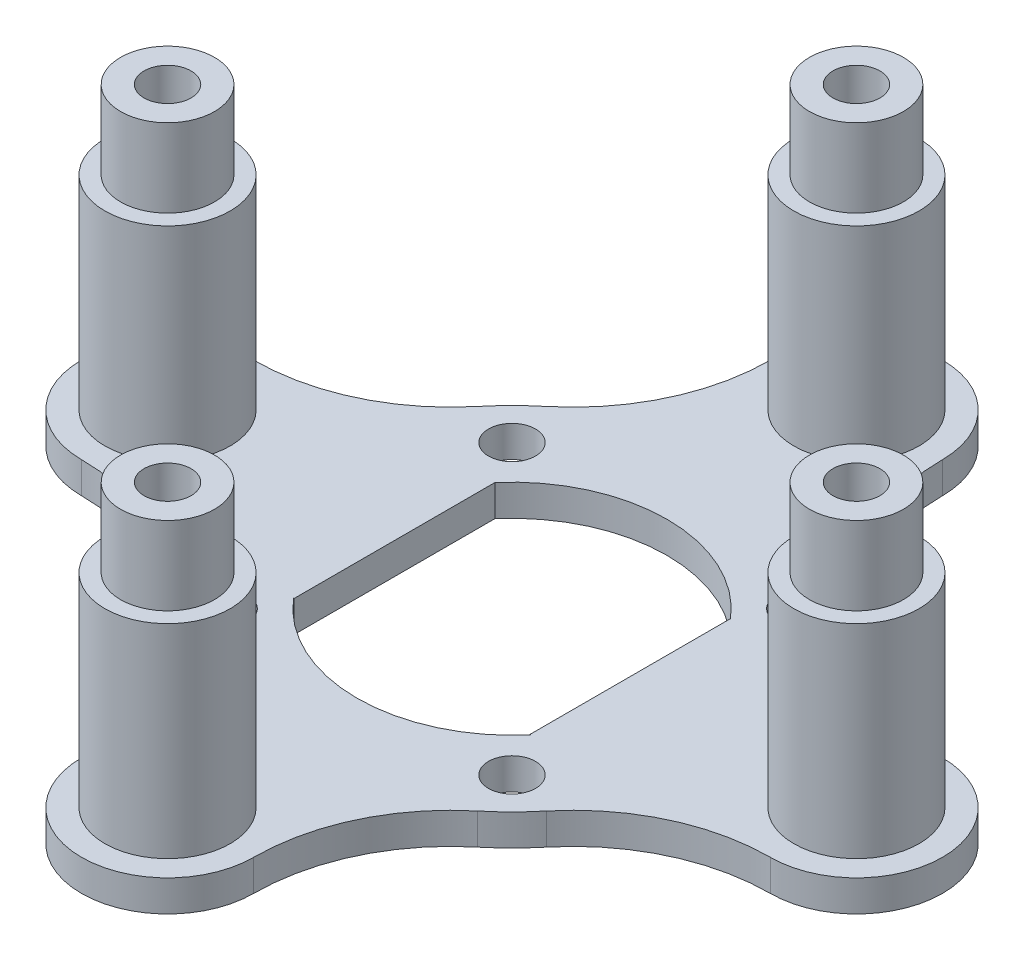
SolidWorks part; units mm, degrees
ref_plane "Front Plane" through (0, 0, 0) normal (0, 0, 1) x (1, 0, 0)
ref_plane "Top Plane" through (0, 0, 0) normal (0, 1, 0) x (1, 0, 0)
ref_plane "Right Plane" through (0, 0, 0) normal (1, 0, 0) x (0, 0, -1)
sketch "Sketch1" plane through (0, 0, 0) normal (0, 1, 0) x (1, 0, 0)
  line L0 (-7.5263, -6.3887) -> (-7.5627, -6.3887)
  line L1 (7.5627, -6.3887) -> (7.5263, -6.3887)
  line L2 (7.5263, -6.3887) -> (7.5263, 6.4316)
  line L3 (-7.5263, 6.4316) -> (-7.5263, -6.3887)
  line L4 (-9.1924, 9.1924) -> (-9.1924, -9.1924) construction
  line L5 (-9.1924, 9.1924) -> (9.1924, 9.1924) construction
  line L6 (-9.1924, -9.1924) -> (9.1924, -9.1924) construction
  line L7 (9.1924, 9.1924) -> (9.1924, -9.1924) construction
  line L8 (-9.1924, 9.1924) -> (9.1924, -9.1924) construction
  line L9 (-9.1924, -9.1924) -> (9.1924, 9.1924) construction
  arc A0 (-7.5627, -6.3887) -> (7.5627, -6.3887) centre (0, 0) ccw
  arc A1 (7.5263, 6.4316) -> (-7.5263, 6.4316) centre (0, 0) ccw
  circle A2 centre (0, 0) radius 15.9
  circle A3 centre (-9.1924, 9.1924) radius 1.5
  circle A4 centre (9.1924, 9.1924) radius 1.5
  circle A5 centre (9.1924, -9.1924) radius 1.5
  circle A6 centre (-9.1924, -9.1924) radius 1.5
  point P24 (0, 0)
  dimension "D1" = 31.8
  dimension "D3" = 9.9
  dimension "D6" = 3
  dimension "D2" = 12.8202
  dimension "D4" = 15.089
  dimension "D5" = 13
  dimension "D7" = 4
sketch "Sketch2" plane through (0, 0, 0) normal (0, 1, 0) x (1, 0, 0)
  line L0 (0, 0) -> (155.6578, 0) construction
  line L1 (-7.5263, 6.4316) -> (-7.5263, -6.3887) construction
  line L2 (-7.5263, -6.3887) -> (-7.5627, -6.3887) construction
  line L3 (7.5627, -6.3887) -> (7.5263, -6.3887) construction
  line L4 (7.5263, -6.3887) -> (7.5263, 6.4316) construction
  line L5 (-7.5263, 6.4316) -> (-7.5263, -6.3887)
  line L6 (-7.5263, -6.3887) -> (-7.5627, -6.3887)
  line L7 (7.5627, -6.3887) -> (7.5263, -6.3887)
  line L8 (7.5263, -6.3887) -> (7.5263, 6.4316)
  circle A0 centre (22, 0) radius 1.5
  circle A1 centre (22, 0) radius 4
  circle A2 centre (22, 0) radius 3
  circle A12 centre (22, 0) radius 5.5
  arc A13 (12.2869, 10.0916) -> (22, 5.5) centre (22, 18.0692) ccw
  arc A14 (12.2869, -10.0916) -> (22, -5.5) centre (22, -18.0692) cw
  circle A15 centre (0, 0) radius 15.9 construction
  circle A16 centre (0, 0) radius 15.9
  arc A17 (10.0916, -12.2869) -> (5.5, -22) centre (18.0692, -22) ccw
  circle A18 centre (0, -22) radius 5.5
  circle A19 centre (0, -22) radius 4
  circle A20 centre (0, -22) radius 3
  circle A21 centre (0, -22) radius 1.5
  arc A22 (-10.0916, -12.2869) -> (-5.5, -22) centre (-18.0692, -22) cw
  arc A23 (-12.2869, -10.0916) -> (-22, -5.5) centre (-22, -18.0692) ccw
  circle A24 centre (-22, 0) radius 5.5
  circle A25 centre (-22, 0) radius 4
  circle A26 centre (-22, 0) radius 3
  circle A27 centre (-22, 0) radius 1.5
  arc A28 (-12.2869, 10.0916) -> (-22, 5.5) centre (-22, 18.0692) cw
  arc A29 (-10.0916, 12.2869) -> (-5.5, 22) centre (-18.0692, 22) ccw
  circle A30 centre (0, 22) radius 5.5
  circle A31 centre (0, 22) radius 4
  circle A32 centre (0, 22) radius 3
  circle A33 centre (0, 22) radius 1.5
  arc A34 (10.0916, 12.2869) -> (5.5, 22) centre (18.0692, 22) cw
  arc A35 (-7.5627, -6.3887) -> (7.5627, -6.3887) centre (0, 0) ccw construction
  arc A36 (7.5263, 6.4316) -> (-7.5263, 6.4316) centre (0, 0) ccw construction
  circle A37 centre (9.1924, 9.1924) radius 1.5 construction
  circle A38 centre (9.1924, -9.1924) radius 1.5 construction
  circle A39 centre (-9.1924, -9.1924) radius 1.5 construction
  circle A40 centre (-9.1924, 9.1924) radius 1.5 construction
  arc A41 (-7.5627, -6.3887) -> (7.5627, -6.3887) centre (0, 0) ccw
  arc A42 (7.5263, 6.4316) -> (-7.5263, 6.4316) centre (0, 0) ccw
  circle A43 centre (9.1924, 9.1924) radius 1.5
  circle A44 centre (9.1924, -9.1924) radius 1.5
  circle A45 centre (-9.1924, -9.1924) radius 1.5
  circle A46 centre (-9.1924, 9.1924) radius 1.5
  point P7 (0, 0)
  point P8 (0, -26.6212)
  point P12 (0, 0)
  point P19 (0, 0)
  point P54 (0, 0)
  dimension "D1" = 3
  dimension "D2" = 6
  dimension "D3" = 8
  dimension "D4" = 11
  dimension "D5" = 22
  dimension "D6" = 4
extrude "Boss-Extrude1" add sketch "Sketch2" along normal blind 2 contours A42 L8 A16 L7 A41 L6 L5 A46 A45 A44 A43 | A16 A22 A18 A17 | L0 A16 A14 A12 | A16 L0 A12 A13 | A12 L0 A1 | A1 L0 A2 | A2 L0 A0 | L0 A12 A1 | L0 A1 A2 | L0 A2 A0 | A18 A19 | A21 | A16 A34 A30 A29 | A30 A31 | A31 A32 | A32 A33 | A24 A25 | A25 A26 | A26 A27 | A16 A28 A24 A23 | A19 region at (22, 0, -1.5671) region at (24.25, 0, 0.0671) region at (22, 0, -3.0894) region at (25.5, 0, 0.0894) region at (22, 0, -4.123) region at (26.75, 0, 0.123) region at (16.6203, 0, -4.8104) region at (16.6203, 0, 4.8104) region at (14.5461, 0, -5.2079) region at (0, 0, -16.124) region at (6.5032, 0, 16.5324) region at (0, 0, -16.6556) region at (0, 0, 27.3444) region at (-16.124, 0, 0) region at (-18.2209, 0, -3.7791) region at (0, 0, 22) region at (-25.8869, 0, 0) region at (-24.9151, 0, 0) region at (-3.8869, 0, -22) region at (-2.9151, 0, -22)
extrude "Boss-Extrude2" add sketch "Sketch2<4>" along normal blind 20 contours A19 A20 | A20 A21 | L0 A1 A2 | L0 A2 A0 | A2 L0 A0 | A1 L0 A2 | A31 A32 | A32 A33 | A25 A26 | A27 | A26 region at (22, 0, -1.5671) region at (24.25, 0, 0.0671) region at (22, 0, -3.0894) region at (25.5, 0, 0.0894) region at (-3.8869, 0, 22) region at (-2.9151, 0, 22) region at (-25.8869, 0, 0) region at (-22, 0, 0) region at (-3.8869, 0, -22) region at (-2.9151, 0, -22)
sketch "Sketch2<4>" plane through (0, 0, 0) normal (0, 1, 0) x (1, 0, 0) same geometry as "Sketch2"
extrude "Cut-Extrude1" cut sketch "Sketch2<5>" against normal blind 5 from surface contours A25 A26 | A31 A32 | A1 L0 A2 | L0 A1 A2 | A19 A20 region at (22, 0, -3.0894) region at (25.5, 0, 0.0894) region at (-3.8869, 0, 22) region at (-25.8869, 0, 0) region at (-3.8869, 0, -22) starting at face at (0, 20, 26)
sketch "Sketch2<5>" plane through (0, 0, 0) normal (0, 1, 0) x (1, 0, 0) same geometry as "Sketch2"
sketch "Sketch3" plane through (0, 0, 0) normal (0, 1, 0) x (1, 0, 0)
  circle A0 centre (0, -22) radius 1.5 construction
  circle A1 centre (0, -22) radius 3 construction
  circle A2 centre (0, -22) radius 4 construction
  circle A3 centre (22, 0) radius 1.5 construction
  circle A4 centre (22, 0) radius 3 construction
  circle A5 centre (22, 0) radius 4 construction
  circle A6 centre (0, 22) radius 1.5 construction
  circle A7 centre (0, 22) radius 3 construction
  circle A8 centre (0, 22) radius 4 construction
  circle A9 centre (-22, 0) radius 1.5 construction
  circle A10 centre (-22, 0) radius 3 construction
  circle A11 centre (-22, 0) radius 4 construction
  circle A12 centre (0, -22) radius 1.5
  circle A13 centre (0, -22) radius 3
  circle A14 centre (0, -22) radius 4
  circle A15 centre (22, 0) radius 1.5
  arc A16 (22, -5.5) -> (22, 5.5) centre (22, 0) ccw
  arc A17 (12.2869, 10.0916) -> (22, 5.5) centre (22, 18.0692) ccw
  arc A18 (12.2869, 10.0916) -> (10.0916, 12.2869) centre (0, 0) ccw
  arc A19 (5.5, 22) -> (10.0916, 12.2869) centre (18.0692, 22) ccw
  arc A20 (5.5, 22) -> (-5.5, 22) centre (0, 22) ccw
  arc A21 (-10.0916, 12.2869) -> (-5.5, 22) centre (-18.0692, 22) ccw
  arc A22 (-10.0916, 12.2869) -> (-12.2869, 10.0916) centre (0, 0) ccw
  arc A23 (-22, 5.5) -> (-12.2869, 10.0916) centre (-22, 18.0692) ccw
  arc A24 (-22, 5.5) -> (-22, -5.5) centre (-22, 0) ccw
  arc A25 (-12.2869, -10.0916) -> (-22, -5.5) centre (-22, -18.0692) ccw
  arc A26 (-12.2869, -10.0916) -> (-10.0916, -12.2869) centre (0, 0) ccw
  arc A27 (-5.5, -22) -> (-10.0916, -12.2869) centre (-18.0692, -22) ccw
  arc A28 (-5.5, -22) -> (5.5, -22) centre (0, -22) ccw
  arc A29 (10.0916, -12.2869) -> (5.5, -22) centre (18.0692, -22) ccw
  arc A30 (10.0916, -12.2869) -> (12.2869, -10.0916) centre (0, 0) ccw
  arc A31 (22, -5.5) -> (12.2869, -10.0916) centre (22, -18.0692) ccw
  arc A32 (22, -5.5) -> (22, 5.5) centre (22, 0) ccw
  arc A33 (12.2869, 10.0916) -> (22, 5.5) centre (22, 18.0692) ccw
  arc A34 (12.2869, 10.0916) -> (10.0916, 12.2869) centre (0, 0) ccw
  arc A35 (5.5, 22) -> (10.0916, 12.2869) centre (18.0692, 22) ccw
  arc A36 (5.5, 22) -> (-5.5, 22) centre (0, 22) ccw
  arc A37 (-10.0916, 12.2869) -> (-5.5, 22) centre (-18.0692, 22) ccw
  arc A38 (-10.0916, 12.2869) -> (-12.2869, 10.0916) centre (0, 0) ccw
  arc A39 (-22, 5.5) -> (-12.2869, 10.0916) centre (-22, 18.0692) ccw
  arc A40 (-22, 5.5) -> (-22, -5.5) centre (-22, 0) ccw
  arc A41 (-12.2869, -10.0916) -> (-22, -5.5) centre (-22, -18.0692) ccw
  arc A42 (-12.2869, -10.0916) -> (-10.0916, -12.2869) centre (0, 0) ccw
  arc A43 (-5.5, -22) -> (-10.0916, -12.2869) centre (-18.0692, -22) ccw
  arc A44 (-5.5, -22) -> (5.5, -22) centre (0, -22) ccw
  arc A45 (10.0916, -12.2869) -> (5.5, -22) centre (18.0692, -22) ccw
  arc A46 (10.0916, -12.2869) -> (12.2869, -10.0916) centre (0, 0) ccw
  arc A47 (22, -5.5) -> (12.2869, -10.0916) centre (22, -18.0692) ccw
  circle A48 centre (22, 0) radius 3
  circle A49 centre (22, 0) radius 4
  circle A50 centre (0, 22) radius 1.5
  circle A51 centre (0, 22) radius 3
  circle A52 centre (0, 22) radius 4
  circle A53 centre (-22, 0) radius 1.5
  circle A54 centre (-22, 0) radius 3
  circle A55 centre (-22, 0) radius 4
  dimension "D1" = 0
